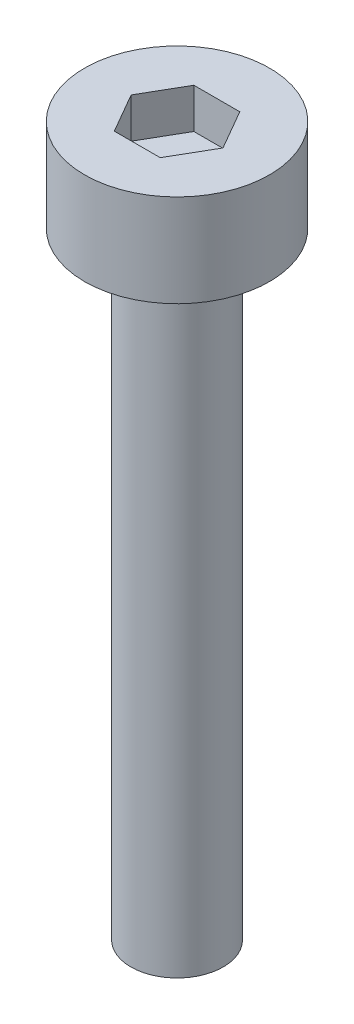
SolidWorks part; units mm, degrees
ref_plane "Front Plane" through (0, 0, 0) normal (0, 0, 1) x (1, 0, 0)
ref_plane "Top Plane" through (0, 0, 0) normal (0, 1, 0) x (1, 0, 0)
ref_plane "Right Plane" through (0, 0, 0) normal (1, 0, 0) x (0, 0, -1)
sketch "Sketch1" plane through (0, 0, 0) normal (0, 1, 0) x (1, 0, 0)
  circle A0 centre (0, 0) radius 1.5
  dimension "D1" = 3
extrude "ScrewShaft" add sketch "Sketch1" along normal blind 20
sketch "Sketch2" plane through (0, 20, 0) normal (0, 1, 0) x (1, 0, 0)
  circle A0 centre (0, 0) radius 3
  dimension "D1" = 6
extrude "Boss-Extrude2" add sketch "Sketch2" along normal blind 3
sketch "Sketch3" plane through (0, 23, 0) normal (0, 1, 0) x (1, 0, 0)
  line L0 (0, 0) -> (0, 1.29) construction
  line L1 (1.4896, 0) -> (0.7448, 1.29)
  line L2 (0.7448, 1.29) -> (-0.7448, 1.29)
  line L3 (-0.7448, 1.29) -> (-1.4896, 0)
  line L4 (-1.4896, 0) -> (-0.7448, -1.29)
  line L5 (-0.7448, -1.29) -> (0.7448, -1.29)
  line L6 (0.7448, -1.29) -> (1.4896, 0)
  circle A0 centre (0, 0) radius 1.29 construction
  dimension "D1" = 2.58
extrude "Cut-Extrude1" cut sketch "Sketch3" against normal blind 1.3
equation "\"X-ROD-SPACING\"=45"
equation "\"Y-ROD-SPACING\"=75"
equation "\"Z-ROD-SPACING\"=17.5"
equation "\"Y-BED-OFFSET\"=2"
equation "\"Y-BED-ROD-INSET\"=3.5"
equation "\"T-SLOT-NUT-FILLET-RADIUS\"=0.5"
equation "\"T-SLOT-SCREW-SHAFT-RADIUS\"=1.55"
equation "\"T-SLOT-SCREW-SHAFT-CUTOUT-LENGTH\"=11"
equation "\"T-SLOT-NUT-DEPTH\"=3.5"
equation "\"T-SLOT-NUT-WIDTH\"=2.85"
equation "\"T-SLOT-NUT-END-DISTANCE\"=8"
equation "\"ACRYLIC-THICKNESS\"=10"
equation "\"ACRYLIC-THICKNESS2\"=4.5"
equation "\"ACRYLIC-TAB-CUTOUT-SIZE\"=\"ACRYLIC-THICKNESS\"+\"ACRYLIC-TAB-TOLERANCE\"*2"
equation "\"ACRYLIC-TAB-WIDTH\"=\"ACRYLIC-THICKNESS\""
equation "\"ACRYLIC-M3-HOLE\"=2.9"
equation "\"SMOOTHROD-CAP-SCREW-DISTANCE\"=20"
equation "\"FRAME-WIDTH-INNER\"=370"
equation "\"NEMA17-HOLE-SPACING\"=31"
equation "\"NEMA17-CENTRAL-CUTOUT\"=22.5"
equation "\"Z-BRACKET-REACH\"=55"
equation "\"TOP-BRACKET-SPACING\"=40"
equation "\"SMOOTHROD-X-LENGTH\"=350"
equation "\"SMOOTHROD-Y-LENGTH\"=350"
equation "\"SMOOTHROD-Z-LENGTH\"=350"
equation "\"SMOOTHROD-TIGHTENING-HEADROOM\"=.25"
equation "\"LEADSCREW-Z-LENGTH\"=300"
equation "\"SCREW-LENGTH-FRAME\"=\"ACRYLIC-THICKNESS\" + 10"
equation "\"SCREW-HEAD-RADIUS\"=6"
equation "\"PRINTED-X-SMOOTHROD-DIAMETER\"=8.8"
equation "\"PRINTED-X-SMOOTHROD-CUTOUT\"=10"
equation "\"PRINTED-X-BASE-HEIGHT\"=10"
equation "\"PRINTED-LM8UU-CUTOUT-SIZE\"=15.5"
equation "\"PRINTED-LM8UU-CUTOUT-LENGTH\"=24.5"
equation "\"PRINTED-X-IDLER-HEIGHT\"=16"
equation "\"PSU-MOUNTING-WIDTH\"=95"
equation "\"PSU-MOUNTING-HEIGHT\"=177"
equation "\"D1@ScrewShaft\"=\"SCREW-LENGTH-FRAME\""
equation "\"D1@Sketch2\"=\"SCREW-HEAD-RADIUS\""
